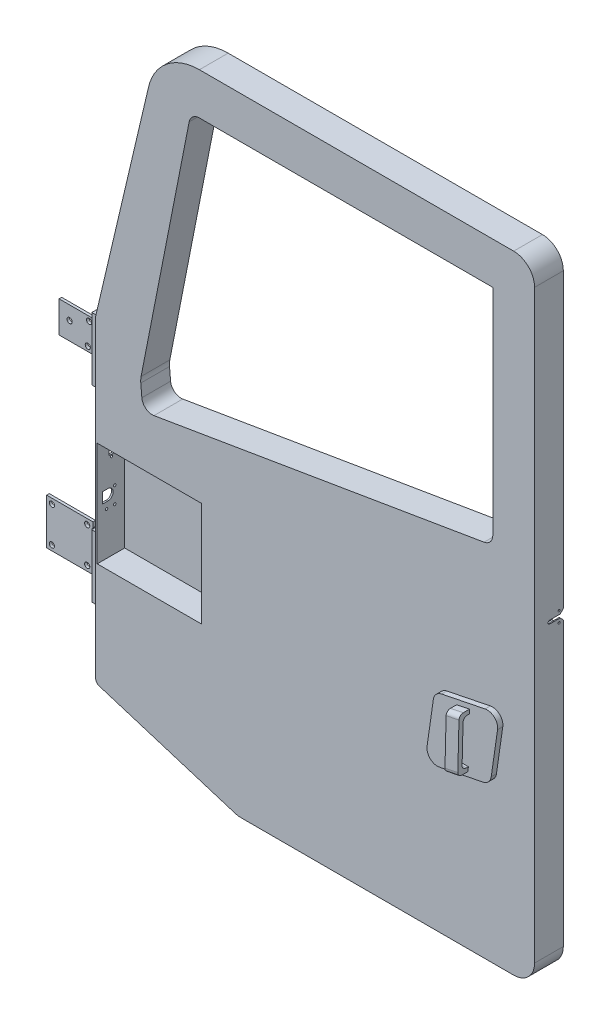
SolidWorks part; units mm, degrees
ref_plane "Front Plane" through (0, 0, 0) normal (0, 0, 1) x (1, 0, 0)
ref_plane "Top Plane" through (0, 0, 0) normal (0, 1, 0) x (1, 0, 0)
ref_plane "Right Plane" through (0, 0, 0) normal (1, 0, 0) x (0, 0, -1)
sketch "Sketch2" plane through (0, 0, 0) normal (0, 0, 1) x (1, 0, 0)
  line L1 (-179.7693, -762.022) -> (482.6, -762.022)
  line L3 (-281.2299, 761.978) -> (482.6, 761.978)
  line L4 (533.4, -711.222) -> (533.4, 711.178)
  line L5 (-459.8603, -656.939) -> (-452.0517, -645.784) construction
  line L6 (-417.9715, 597.0829) -> (44.2876, -63.266) construction
  line L8 (-524.4721, -657.2008) -> (-194.8579, -759.7295)
  line L9 (-306.1723, 639.7777) -> (-423.0219, 45.4039)
  line L10 (-423.7768, 31.1096) -> (-421.1458, 1.4921)
  line L14 (-281.2299, 660.378) -> (431.8, 660.378)
  line L16 (431.7996, 138.4174) -> (431.8, 660.378)
  line L17 (431.8, -660.422) -> (431.8, 660.378) construction
  line L18 (-172.0509, -660.422) -> (431.8, -660.422) construction
  line L19 (-533.4, 116.926) -> (-405.8883, 659.253)
  line L20 (-367.7549, -599.547) -> (-172.0509, -660.422) construction
  line L21 (-55.7209, -79.6007) -> (521.0599, 744.3665) construction
  line L22 (-306.1723, 639.7777) -> (-424.4164, 38.3105) construction
  line L23 (-424.4164, 38.3105) -> (-367.7549, -599.547) construction
  line L24 (-414.3579, -691.4526) -> (-194.8579, -759.7295) construction
  line L25 (-179.7693, -762.022) -> (482.6, -762.022)
  line L27 (-281.2299, 761.978) -> (482.6, 761.978)
  line L28 (533.4, -711.222) -> (533.4, 711.178)
  line L29 (-459.8603, -656.939) -> (-452.0517, -645.784) construction
  line L30 (-417.9715, 597.0829) -> (44.2876, -63.266) construction
  line L31 (-533.4, 116.926) -> (-466.2749, -638.723) construction
  line L32 (-391.6402, -21.3099) -> (410.6048, 113.3679)
  line L33 (-55.7209, -79.6007) -> (521.0599, 744.3665) construction
  line L34 (-281.2299, 761.978) -> (482.6, 761.978)
  line L35 (-533.4, 116.926) -> (-533.4, -645.074)
  line L36 (-179.7693, -762.022) -> (482.6, -762.022)
  line L37 (533.4, 711.178) -> (533.4, -711.222)
  line L38 (-417.9715, 597.0829) -> (44.2876, -63.266) construction
  line L39 (-471.5639, -673.6583) -> (-452.0517, -645.784) construction
  line L40 (-405.8883, 659.253) -> (-528.8132, 33.9764) construction
  line L41 (-55.7209, -79.6007) -> (521.0599, 744.3665) construction
  arc A0 (-405.8883, 659.253) -> (-281.2299, 761.978) centre (-281.2299, 634.978) cw
  arc A3 (533.4, 711.178) -> (482.6, 761.978) centre (482.6, 711.178) ccw
  arc A4 (482.6, -762.022) -> (533.4, -711.222) centre (482.6, -711.222) ccw
  arc A5 (-194.8579, -759.7295) -> (-179.7693, -762.022) centre (-179.7693, -711.222) ccw
  arc A7 (-367.7549, -599.547) -> (-367.7549, -599.547) centre (-367.7549, -599.547) ccw
  arc A8 (-172.0509, -660.422) -> (-172.0509, -660.422) centre (-172.0509, -660.422) ccw
  arc A9 (431.8, -660.422) -> (431.8, -660.422) centre (431.8, -660.422) ccw
  arc A10 (431.8, 660.378) -> (431.8, 660.378) centre (431.8, 660.378) ccw
  arc A11 (-306.1723, 639.7777) -> (-281.2299, 660.378) centre (-281.2299, 634.978) cw
  arc A12 (-423.0219, 45.4039) -> (-423.7768, 31.1096) centre (-373.176, 35.6045) ccw
  arc A13 (-424.4164, 38.3105) -> (-424.4164, 38.3105) centre (-424.4164, 38.3105) ccw construction
  arc A16 (-466.2749, -638.723) -> (-414.3579, -691.4526) centre (-391.0208, -616.5518) ccw construction
  arc A17 (-533.4, -645.074) -> (-524.4721, -657.2008) centre (-520.7, -645.074) ccw
  arc A18 (-528.8132, 33.9764) -> (-533.4, 116.926) centre (-501.9071, 77.0658) ccw construction
  arc A19 (431.7996, 138.4174) -> (410.6048, 113.3679) centre (406.3996, 138.4174) cw
  arc A20 (-391.6402, -21.3099) -> (-421.1458, 1.4921) centre (-395.8454, 3.7395) cw
  point P0 (0, 0)
  point P16 (-533.4, -0.0244)
  point P56 (0, 0)
  point P61 (0, 0)
  dimension "D3" = 127
  dimension "D6" = 50.8
  dimension "D8" = 50.8
  dimension "D2" = 12.7
  dimension "D9" = 25.4
  dimension "D1" = 1066.8
  dimension "D4" = 1524
  dimension "D5" = 762
  dimension "D7" = 101.6
extrude "Boss-Extrude1" add sketch "Sketch2" along normal mid plane 69.85 contours L8 A5 L1 A4 L4 A3 L3 A0 L10 A12 L9 A11 L14 L16 A20 region at (22.1716, -171.0663, 0)
ref_plane "bottom" through (0, -762.022, 0) normal (0, -1, 0) x (-1, 0, 0)
ref_plane "top door check" through (0, -158.772, 0) normal (0, -1, 0) x (-1, 0, 0)
ref_plane "door check mid" through (0, -176.2345, 0) normal (0, -1, 0) x (-1, 0, 0)
ref_plane "bottom door check" through (0, -193.697, 0) normal (0, -1, 0) x (-1, 0, 0)
ref_plane "top hinge top hole" through (0, 66.653, 0) normal (0, -1, 0) x (-1, 0, 0)
ref_plane "top hinge middle hole" through (0, 44.428, 0) normal (0, -1, 0) x (-1, 0, 0)
ref_plane "top hinge bottom hole" through (0, 12.678, 0) normal (0, -1, 0) x (-1, 0, 0)
ref_plane "bottome hinge top hole" through (0, -363.5595, 0) normal (0, -1, 0) x (-1, 0, 0)
ref_plane "bottom hinge bottom hole" through (0, -449.2845, 0) normal (0, -1, 0) x (-1, 0, 0)
ref_plane "Plane1" through (0, 0, 31.75) normal (0, 0, 1) x (1, 0, 0)
sketch "Sketch3" plane through (0, 0, 34.925) normal (0, 0, 1) x (1, 0, 0)
  line L0 (320.1959, -245.101) -> (425.9265, -223.6716)
  line L3 (314.9201, -401.6691) -> (420.6507, -380.2397)
  line L4 (456.113, -252.1835) -> (440.7462, -358.9639)
  line L5 (300.1004, -266.3768) -> (284.7336, -373.1572)
  line L6 (310.4001, -194.8067) -> (287.3499, -354.9772) construction
  line L7 (-487.6326, -408.8312) -> (533.4008, -201.8888) construction
  line L8 (-457.3598, -558.1943) -> (563.6737, -351.2518) construction
  line L9 (461.2461, -216.515) -> (438.1959, -376.6855) construction
  line L10 (373.0612, -234.3863) -> (367.7854, -390.9544) construction
  line L11 (360.2667, -236.9795) -> (354.9908, -393.5476)
  line L12 (385.8558, -231.7931) -> (380.58, -388.3612)
  line L13 (360.3684, -233.9586) -> (355.0926, -390.5267) construction
  line L14 (385.754, -234.814) -> (380.4782, -391.3821) construction
  arc A0 (300.1004, -266.3768) -> (320.1959, -245.101) centre (325.2414, -269.9949) cw
  arc A1 (284.7336, -373.1572) -> (314.9201, -401.6691) centre (309.8746, -376.7752) ccw
  arc A2 (440.7462, -358.9639) -> (420.6507, -380.2397) centre (415.6052, -355.3458) cw
  arc A3 (456.113, -252.1835) -> (425.9265, -223.6716) centre (430.972, -248.5655) ccw
  dimension "D3" = 25.4
  dimension "D1" = 152.4
  dimension "D2" = 152.4
  dimension "D4" = 12.7
  dimension "D5" = 12.7
extrude "Boss-Extrude2" add sketch "Sketch3" along normal blind 12.7 contours L5 A1 L3 L11 L0 A0 | L4 A3 L0 L12 L3 A2 | L12 L0 L11 L3 region at (325.2101, -323.7797, 34.925) region at (370.4233, -312.6704, 34.925) region at (415.6365, -301.561, 34.925)
sketch "Sketch5" plane through (0, 0, 34.925) normal (0, 0, 1) x (1, 0, 0)
  line L6 (-179.7693, -762.022) -> (482.6, -762.022)
  line L12 (-179.7693, -762.022) -> (482.6, -762.022)
  line L28 (387.9598, -243.0291) -> (384.7172, -375.8602)
  line L29 (353.4927, -382.1888) -> (356.7353, -249.3577)
  line L30 (387.9598, -243.0291) -> (356.7353, -249.3577)
  line L31 (384.7172, -375.8602) -> (353.4927, -382.1888)
  line L32 (320.1959, -245.101) -> (425.9265, -223.6716) construction
  line L33 (314.9201, -401.6691) -> (420.6507, -380.2397) construction
  line L34 (320.1959, -245.101) -> (425.9265, -223.6716) construction
  line L35 (314.9201, -401.6691) -> (420.6507, -380.2397) construction
  dimension "D2" = 11.43
  dimension "D3" = 11.43
  dimension "D1" = 0
extrude "Boss-Extrude4" add sketch "Sketch5" along normal blind 38.1 contours L31 L28 L30 L29 region at (370.7262, -312.609, 34.925)
sketch "Sketch6" plane through (393.6581, -9.61, 0) normal (0.9997, -0.0244, 0) x (0, 0, -1)
  line L9 (-47.625, -356.1994) -> (-62.865, -356.1994)
  line L10 (-62.865, -356.1994) -> (-62.865, -243.6487)
  line L11 (-62.865, -243.6487) -> (-47.625, -243.6487)
  line L12 (-47.625, -356.1994) -> (-62.865, -356.1994)
  line L13 (-62.865, -356.1994) -> (-62.865, -243.6487)
  line L14 (-62.865, -243.6487) -> (-47.625, -243.6487)
  line M5 (-47.625, -366.3594) -> (-47.625, -233.4887)
  dimension "D1" = 10.16
extrude "Cut-Extrude6" cut sketch "Sketch6" against normal through all and the other way through all contours L14 L13 L12 M5 region at (386.3385, -309.4447, 55.245)
fillet "Fillet5" radius 10.16 4 edges at (369.1049, -379.0245, 73.025) (369.4394, -365.3242, 62.865) (372.1861, -252.8071, 62.865) (372.3476, -246.1934, 73.025)
sketch "Sketch7" plane through (-533.4, 59.3738, 0) normal (1, 0, 0) x (0, 0, 1)
  line L0 (0, 821.3958) -> (0, -702.6042) construction
  line L1 (34.925, 821.3958) -> (-34.925, 821.3958) construction
  line L2 (34.925, -702.6042) -> (-34.925, -702.6042) construction
  line L4 (-31.75, -57.5522) -> (31.75, -57.5522)
  line L5 (-31.75, -57.5522) -> (-31.75, 94.8478)
  line L6 (-31.75, 94.8478) -> (31.75, 94.8478)
  line L11 (31.75, -57.5522) -> (31.75, 94.8478)
  line L12 (-31.75, -57.5522) -> (31.75, 94.8478) construction
  line L13 (-31.75, 94.8478) -> (31.75, -57.5522) construction
  line L19 (34.925, -57.5522) -> (-34.925, -57.5522) construction
  line L21 (-31.75, 552.0478) -> (31.75, 552.0478)
  line L28 (-31.75, 552.0478) -> (-31.75, 399.6478)
  line L29 (-31.75, 399.6478) -> (31.75, 399.6478)
  line L30 (31.75, 552.0478) -> (31.75, 399.6478)
  line L31 (-31.75, 552.0478) -> (31.75, 399.6478) construction
  line L32 (-31.75, 399.6478) -> (31.75, 552.0478) construction
  point P6 (0, 18.6478)
  point P13 (0, 475.8478)
  dimension "D1" = 63.5
  dimension "D2" = 152.4
  dimension "D4" = 304.8
extrude "Boss-Extrude5" add sketch "Sketch7" against normal blind 12.7
sketch "Sketch16" plane through (0, 0, 34.925) normal (0, 0, 1) x (1, 0, 0)
  line L1 (-529.59, -148.3099) -> (-529.59, -402.3099)
  line L3 (-275.59, -402.3099) -> (-275.59, -148.3099)
  line L5 (-533.4, 116.926) -> (-533.4, -645.074) construction
  line L6 (-529.59, -148.3099) -> (-275.59, -148.3099)
  line L7 (-529.59, -402.3099) -> (-275.59, -402.3099)
  dimension "D1" = 254
  dimension "D2" = 127
  dimension "D3" = 254
  dimension "D4" = 3.81
extrude "Cut-Extrude8" cut sketch "Sketch16" against normal blind 66.675
sketch "Sketch20" plane through (-533.4, 0, 0) normal (-1, 0, 0) x (0, 0, 1)
  line L0 (-38.4175, -176.2345) -> (38.4175, -176.2345) construction
  line L1 (-6.35, -188.9345) -> (6.35, -188.9345)
  line L2 (-6.35, -188.9345) -> (-6.35, -163.5345)
  line L3 (-6.35, -163.5345) -> (6.35, -163.5345)
  line L4 (6.35, -188.9345) -> (6.35, -163.5345)
  line L5 (-6.35, -188.9345) -> (6.35, -163.5345) construction
  line L6 (-6.35, -163.5345) -> (6.35, -188.9345) construction
  line L7 (-38.4175, -158.772) -> (38.4175, -158.772) construction
  line L8 (6.35, -176.2345) -> (-6.35, -176.2345) construction
  circle A0 centre (0, -158.772) radius 2.54
  circle A1 centre (0, -193.697) radius 2.54
  point P0 (0, -176.2345)
  dimension "D3" = 5.08
  dimension "D1" = 12.7
  dimension "D2" = 25.4
extrude "Cut-Extrude12" cut sketch "Sketch20" against normal up to surface (3.81 mm away) contours A0 | L4 L3 L2 L1 | A1 up to face at (-529.59, -275.3099, 1.5875)
sketch "Sketch21" plane through (0, 0, 0) normal (0, 0, 1) x (1, 0, 0)
  line L0 (-38.4175, 66.653) -> (38.4175, 66.653) construction
  line L1 (-202.423, 66.653) -> (-1027.3811, 66.653) construction
  line L2 (-212.5576, 44.428) -> (-1027.3811, 44.428) construction
  line L3 (-38.4175, 44.428) -> (38.4175, 44.428) construction
  line L4 (-212.5576, 12.678) -> (-1027.3811, 12.678) construction
  line L5 (-38.4175, 12.678) -> (38.4175, 12.678) construction
  line L6 (-546.1, 116.926) -> (-546.1, -35.474) construction
  line L7 (-558.8, 66.653) -> (-546.1, 66.653)
  line L8 (-558.8, 66.653) -> (-558.8, 12.678)
  line L9 (-558.8, 12.678) -> (-546.1, 12.678)
  line L10 (-546.1, 66.653) -> (-546.1, 12.678)
  line L11 (-654.05, 77.448) -> (-654.05, 1.248)
  line L12 (-654.05, 77.448) -> (-558.8, 77.448)
  line L15 (-558.8, 77.448) -> (-558.8, 12.678)
  line L16 (-654.05, 77.448) -> (-558.8, 12.678) construction
  line L17 (-654.05, 10.0872) -> (-558.8, 77.448) construction
  line L18 (-654.05, 1.248) -> (-558.8, 1.248)
  line L19 (-558.8, 12.678) -> (-558.8, 1.248)
  circle A0 centre (-584.2, 12.678) radius 6.35
  circle A1 centre (-628.65, 44.428) radius 6.35
  circle A2 centre (-581.025, 66.653) radius 6.35
  point P18 (-605.4912, 44.428)
  dimension "D2" = 12.7
  dimension "D3" = 25.4
  dimension "D4" = 69.85
  dimension "D5" = 22.225
  dimension "D6" = 95.25
  dimension "D9" = 64.77
  dimension "D1" = 12.7
  dimension "D7" = 76.2
  dimension "D8" = 33.02
extrude "Boss-Extrude8" add sketch "Sketch21" along normal mid plane 6.35 contours L19 L8 L15 L12 L11 L18 A2 A1 A0 | L10 L7 L8 L9 region at (-552.45, 39.6655, 0) region at (-606.8928, 39.2427, 0)
sketch "Sketch26" plane through (0, 0, 0) normal (0, 0, 1) x (1, 0, 0)
  line L0 (-193.6896, -363.5595) -> (-881.8717, -363.5595) construction
  line L1 (-38.4175, -363.5595) -> (38.4175, -363.5595) construction
  line L2 (-133.4597, -449.2845) -> (-881.8717, -449.2845) construction
  line L3 (-38.4175, -449.2845) -> (38.4175, -449.2845) construction
  line L4 (-625.8948, -363.5595) -> (-625.8948, -449.2845) construction
  line L5 (-625.8948, -406.422) -> (-892.4677, -406.422) construction
  line L6 (-546.1, -340.274) -> (-546.1, -492.674) construction
  line L7 (-571.5, -449.2845) -> (-546.1, -449.2845)
  line L8 (-571.5, -449.2845) -> (-571.5, -363.5595)
  line L9 (-571.5, -363.5595) -> (-546.1, -363.5595)
  line L10 (-546.1, -449.2845) -> (-546.1, -363.5595)
  line L11 (-571.5, -449.2845) -> (-546.1, -363.5595) construction
  line L12 (-571.5, -363.5595) -> (-546.1, -449.2845) construction
  point P12 (-558.8, -406.422)
  dimension "D1" = 25.4
extrude "Boss-Extrude12" add sketch "Sketch26" along normal mid plane 12.7
sketch "Sketch27" plane through (0, 0, 0) normal (0, 0, 1) x (1, 0, 0)
  line L0 (-211.2814, -363.5595) -> (-919.4505, -363.5595) construction
  line L1 (-38.4175, -363.5595) -> (38.4175, -363.5595) construction
  line L2 (-201.3631, -449.2845) -> (-928.7076, -449.2845) construction
  line L3 (-38.4175, -449.2845) -> (38.4175, -449.2845) construction
  line L4 (-571.5, -363.5595) -> (-571.5, -449.2845) construction
  line L5 (-631.7994, -363.5595) -> (-631.7994, -449.2845) construction
  line L6 (-631.7994, -406.422) -> (-919.4505, -406.422) construction
  line L8 (-684.2125, -461.9845) -> (-571.5, -461.9845)
  line L9 (-684.2125, -461.9845) -> (-684.2125, -350.8595)
  line L10 (-684.2125, -350.8595) -> (-571.5, -350.8595)
  line L11 (-571.5, -461.9845) -> (-571.5, -350.8595)
  line L12 (-684.2125, -461.9845) -> (-571.5, -350.8595) construction
  line L13 (-684.2125, -350.8595) -> (-571.5, -461.9845) construction
  circle A0 centre (-585.7875, -363.5595) radius 6.35
  circle A2 centre (-671.5125, -449.2845) radius 6.35
  circle A4 centre (-585.7875, -449.2845) radius 6.35
  circle A5 centre (-671.5125, -363.5595) radius 6.35
  point P22 (-627.8563, -406.422)
  dimension "D1" = 12.7
  dimension "D2" = 100.0125
  dimension "D3" = 14.2875
  dimension "D4" = 12.7
extrude "Boss-Extrude13" add sketch "Sketch27" along normal mid plane 6.35
sketch "Sketch28" plane through (-533.4, 0, 0) normal (-1, 0, 0) x (0, 0, 1)
  line L1 (9.225, -256.897) -> (22.225, -256.897)
  line L3 (9.225, -282.897) -> (22.225, -282.897)
  line L4 (22.225, -256.897) -> (22.225, -282.897)
  line L5 (34.925, -245.101) -> (34.925, -223.6716) construction
  line L6 (-38.4175, -193.697) -> (38.4175, -193.697) construction
  arc A6 (9.225, -256.897) -> (9.225, -282.897) centre (9.225, -269.897) ccw
  circle A7 centre (-7.705, -258.147) radius 3
  circle A8 centre (-7.705, -298.147) radius 3
  circle A9 centre (12.295, -298.147) radius 3
  point P7 (-3.775, -269.897)
  point P16 (22.225, -269.897)
  dimension "D4" = 40
  dimension "D5" = 26
  dimension "D6" = 26
  dimension "D1" = 11.75
  dimension "D2" = 3.93
  dimension "D3" = 20
  dimension "D8" = 12.7
  dimension "D7" = 6
  dimension "D9" = 13
  dimension "D10" = 76.2
extrude "Cut-Extrude13" cut sketch "Sketch28" against normal up to surface (3.81 mm away) contours L1 A6 L3 L4 | A8 | A9 | A7 region at (-533.4, -269.897, 10.4385) region at (-533.4, -298.147, -7.705) region at (-533.4, -298.147, 12.295) up to face at (-529.59, -176.2345, 0)
sketch "Sketch29" plane through (533.4, 0, 0) normal (1, 0, 0) x (0, 0, -1)
  line L0 (34.925, -762.022) -> (34.925, -15.897)
  line L1 (34.925, -711.222) -> (34.925, 711.178) construction
  line L2 (27.305, -15.897) -> (1.9385, -15.897)
  line L3 (34.925, -0.022) -> (34.925, -23.517)
  line L4 (1.9385, -7.642) -> (27.305, -7.642)
  line L5 (27.305, -7.642) -> (34.925, -0.022)
  line L6 (27.305, -15.897) -> (34.925, -23.517)
  arc A0 (1.9385, -7.642) -> (1.9385, -15.897) centre (1.9385, -11.7695) ccw
  line M2 (34.925, -711.222) -> (34.925, 711.178)
extrude "Cut-Extrude14" cut sketch "Sketch29" against normal blind 2.54 contours L4 A0 L2 L6 L0 L5 M2 region at (533.4, -11.7695, -19.3332)
sketch "Sketch30" plane through (0, 0, -34.925) normal (0, 0, -1) x (-1, 0, 0)
  line L0 (-530.86, -11.7695) -> (-530.86, 13.6305)
  line L1 (-530.86, -23.517) -> (-530.86, -0.022) construction
  line L2 (-530.86, 13.6305) -> (-505.46, 13.6305)
  line L3 (-505.46, 13.6305) -> (-505.46, -37.1695)
  line L4 (-505.46, -37.1695) -> (-530.86, -37.1695)
  line L5 (-530.86, -37.1695) -> (-530.86, -11.7695)
extrude "Cut-Extrude15" cut sketch "Sketch30" against normal blind 38.1
sketch "Sketch31" plane through (533.4, 0, 0) normal (1, 0, 0) x (0, 0, -1)
  line L0 (34.925, -11.7695) -> (34.925, 0.9305)
  line L1 (34.925, -37.1695) -> (34.925, 13.6305) construction
  line L2 (34.925, -0.022) -> (34.925, 711.178) construction
  line L3 (34.925, 0.9305) -> (24.765, 0.9305)
  line L4 (24.765, 0.9305) -> (24.765, -24.4695)
  circle A0 centre (24.765, 0.9305) radius 2.54
  circle A1 centre (24.765, -24.4695) radius 2.54
extrude "Cut-Extrude16" cut sketch "Sketch31" against normal blind 10.668 contours L4 A0 L3 | L3 A0 L4 | A1 region at (533.4, -0.1475, -25.843) region at (533.4, 1.2898, -24.4057) region at (533.4, -22.7243, -26.5103)
equation "\"doorwidth\"= 42in"
equation "\"D1@Sketch2\"=\"doorwidth\""
equation "\"doorheight\"= 60in"
equation "\"D4@Sketch2\"=\"doorheight\""
equation "\"doorthickness\"= 2.75in"
equation "\"D1@Boss-Extrude1\"=\"doorthickness\""
equation "\"hingewidth\"= 2.5in"
equation "\"hingeheight\"= 6in"
equation "\"distanceofhinges\"= 12in"
equation "\"D1@Sketch7\"=\"hingewidth\""
equation "\"D2@Sketch7\"=\"hingeheight\""
equation "\"D4@Sketch7\"=\"distanceofhinges\""
